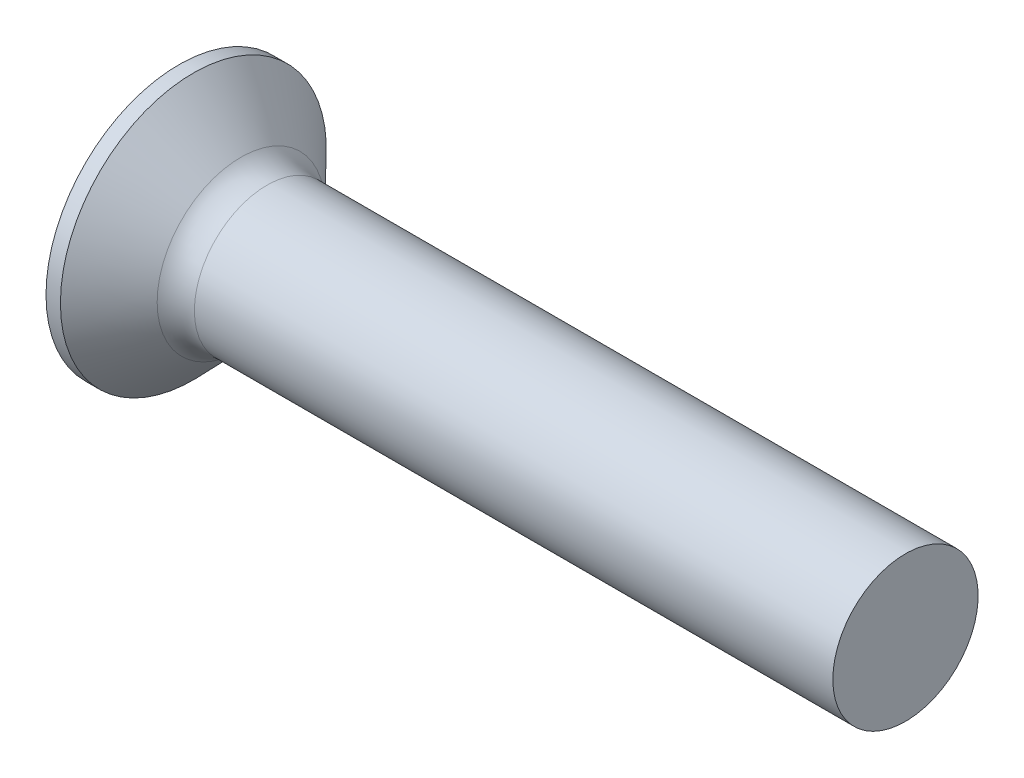
SolidWorks part; units mm, degrees
revolve "Base-Revolve" add sketch "BodySke" angle 360 about L5 other way angle 60
sketch "BodySke" plane through (0, 0, 0) normal (0, 0, 1) x (1, 0, 0)
  line L0 (0, 0) -> (0, 9.15)
  line L1 (0, 9.15) -> (0.9924, 9.15)
  line L2 (5, 5) -> (50, 5)
  line L3 (50, 5) -> (50, 0)
  line L4 (50, 0) -> (0, 0)
  line L5 (-6.35, 0) -> (82.55, 0) construction
  line L6 (5, -5) -> (50, -5) construction
  line L7 (0.9924, -9.15) -> (5, -5) construction
  line L8 (0.9924, 9.15) -> (5, 5)
  line L9 (0, -9.15) -> (0.9924, -9.15) construction
  line L10 (6.5, 6.5875) -> (6.5, -2.9375) construction
  line L11 (0, 6.35) -> (0, -3.175) construction
  dimension "Diameter" = 10
  dimension "D6" = 0.9924
cosmetic thread "ThreadCosmetic" [suppressed] parameters "Thread_length"=43.5, "Thread_minor"=7.9248
ref_plane "Plane1" through (0, 0, 0) normal (0, 0, 1) x (1, 0, 0)
ref_plane "Plane2" through (0, 0, 0) normal (0, 1, 0) x (1, 0, 0)
ref_plane "Plane3" through (0, 0, 0) normal (1, 0, 0) x (0, 0, -1)
fillet "Fillet1" radius 2.5 1 edges at (5, 0, 5)
sketch "Sketch3" plane through (0, 0, 0) normal (-1, 0, 0) x (0, 0, 1)
  line L0 (-1.08, 4.9) -> (1.08, 4.9)
  line L1 (1.08, 4.9) -> (1.08, -4.9)
  line L2 (1.08, -4.9) -> (-1.08, -4.9)
  line L3 (-1.08, -4.9) -> (-1.08, 4.9)
  dimension "Cross_dia" = 9.8
  dimension "Cross_width" = 2.16
  dimension "D1" = 4.9
  dimension "D2" = 1.08
ref_plane "Plane4" through (5.64, 0, 0) normal (-1, 0, 0) x (0, 0, 1)
sketch "Sketch4" plane through (5.64, 0, 0) normal (-1, 0, 0) x (0, 0, 1)
  line L0 (-1.08, 2.088) -> (1.08, 2.088)
  line L3 (1.08, 2.088) -> (1.08, -2.088)
  line L4 (1.08, -2.088) -> (-1.08, -2.088)
  line L5 (-1.08, -2.088) -> (-1.08, 2.088)
  dimension "D2" = 4.176
  dimension "D1" = 2.16
  dimension "D4" = 2.088
  dimension "D3" = 1.08
loft "Recess" cut profiles "Sketch3", "Sketch4"
pattern_circular "RecPat" count 2 every 90 about axis through (-6.35, 0, 0) along (1, 0, 0) of "Recess"
sketch "RecCorSke" plane through (0, 0, 0) normal (0, 0, 1) x (1, 0, 0)
  line L0 (-3.175, 0) -> (15.875, 0) construction
  line L2 (0, 0) -> (0, 2.3249)
  line L3 (0, 2.3249) -> (5.64, 1.9305)
  line L4 (5.64, 1.9305) -> (6.2673, 0)
  line L5 (6.2673, 0) -> (0, 0)
revolve "RecessCore" cut sketch "RecCorSke" angle 360 about L0
sketch "ThdSchSke" plane through (0, 0, 0) normal (0, 0, 1) x (1, 0, 0)
  line L0 (6.5, -3.9624) -> (5.7735, -5)
  line L1 (6.5, -3.9624) -> (7.2265, -5)
  line L2 (7.2265, -5) -> (7.2265, -6.25)
  line L3 (-3.175, 0) -> (5.1513, 0) construction
  line L5 (7.2265, -6.25) -> (5.7735, -6.25)
  line L6 (5.7735, -6.25) -> (5.7735, -5)
  line L7 (0, 9.15) -> (0, -9.15) construction
  dimension "Diameter" = 10
  dimension "Thread_minor" = 7.9248
  dimension "Start" = 6.5
revolve "ThreadSchematic" [suppressed] cut sketch "ThdSchSke" angle 360 about L3
pattern_linear "ThdSchPat" [suppressed]
equation "\"D1@Sketch3\" = \"Cross_dia@Sketch3\" / 2"
equation "\"D2@Sketch3\" = \"Cross_width@Sketch3\" / 2"
equation "\"Depth@RecCorSke\" = \"Cross_depth@Plane4\""
equation "\"D1@Sketch4\" = \"Cross_width@Sketch3\""
equation "\"D2@Sketch4\" = \"Cross_dia@Sketch3\" - 2.0 * \"Cross_depth@Plane4\" * tan(26.5  * 0.017453292)"
equation "\"D3@Sketch4\" = \"D1@Sketch4\" / 2"
equation "\"D4@Sketch4\" = \"D2@Sketch4\" / 2"
equation "\"Thread_length@ThreadCosmetic\" = ((sgn( (\"Length@BodySke\" - \"Advance@BodySke\" * 1.0 - \"Head_ht@BodySke\" ) - \"Thread_nom@BodySke\" )-1)*( (\"Length@BodySke\" - \"Advance@BodySke\" * 1.0 - \"Head_ht@BodySke\" ) - \"Thread_nom@BodySke\" ))/-2+ \"Thread_nom@BodySke\""
equation "\"Thread_minor@ThdSchSke\" = \"Thread_minor@ThreadCosmetic\""
equation "\"Diameter@ThdSchSke\" = \"Diameter@BodySke\""
equation "\"Overcut@ThdSchSke\" = \"Diameter@BodySke\" * 1.25"
equation "\"Start@ThdSchSke\" = 0.000001 + \"Length@BodySke\" - \"Thread_length@ThreadCosmetic\"  '---Countersunk---"
equation "\"Num_threads@ThdSchPat\" = int( \"Thread_length@ThreadCosmetic\" / \"Advance@BodySke\" + 0.999 )  + 1"
equation "\"Advance@ThdSchPat\" = \"Thread_length@ThreadCosmetic\" /  (\"Num_threads@ThdSchPat\" - 1) 'relax it"
